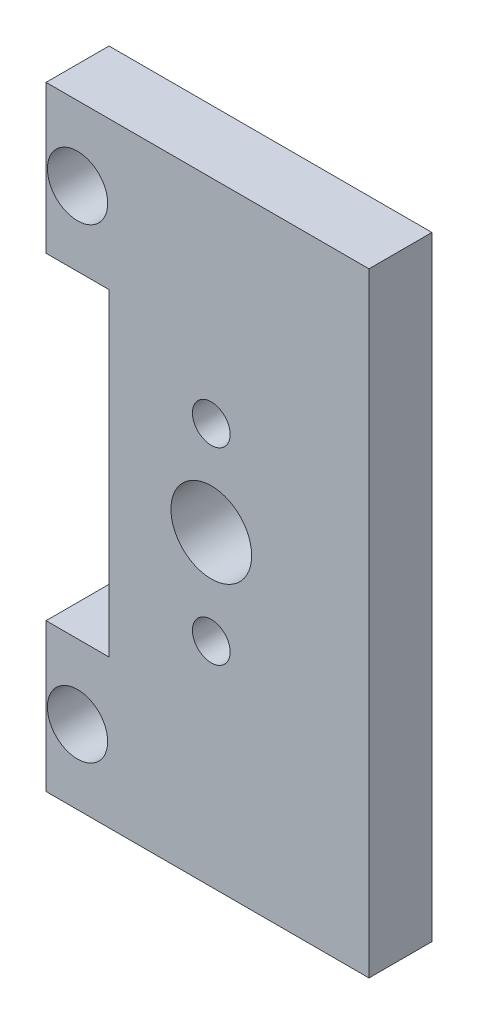
SolidWorks part; units mm, degrees
ref_plane "Front Plane" through (0, 0, 0) normal (0, 0, 1) x (1, 0, 0)
ref_plane "Top Plane" through (0, 0, 0) normal (0, 1, 0) x (1, 0, 0)
ref_plane "Right Plane" through (0, 0, 0) normal (1, 0, 0) x (0, 0, -1)
sketch "Sketch2" plane through (0, 0, 0) normal (0, 0, 1) x (1, 0, 0)
  line L0 (15.24, 14.4925) -> (0, 14.4925) construction
  line L1 (0, 0) -> (15.24, 0)
  line L2 (0, 0) -> (0, 28.985)
  line L5 (0, 28.985) -> (15.24, 28.985)
  line L6 (15.24, 0) -> (15.24, 28.985)
  line L7 (0, 6.985) -> (2.9718, 6.985)
  line L8 (0, 6.985) -> (0, 22)
  line L9 (0, 22) -> (2.9718, 22)
  line L10 (2.9718, 6.985) -> (2.9718, 22)
  circle A0 centre (1.4859, 25.4925) radius 1.4224
  circle A2 centre (1.4859, 3.4925) radius 1.4224
  circle A3 centre (7.7978, 14.4925) radius 1.905
  circle A4 centre (7.7978, 10.0475) radius 0.889
  circle A5 centre (7.7978, 18.9375) radius 0.889
  point P18 (0, 0)
  dimension "D3" = 6.985
  dimension "D7" = 1.4859
  dimension "D6" = 2.8448
  dimension "D9" = 3.81
  dimension "D11" = 1.778
  dimension "D1" = 2.9718
  dimension "D2" = 6.985
  dimension "D4" = 15.24
  dimension "D5" = 15.015
  dimension "D8" = 3.4925
  dimension "D10" = 4.826
  dimension "D12" = 4.445
extrude "Boss-Extrude1" add sketch "Sketch2" along normal blind 2.9718 contours L0 L6 L5 L2 L9 L10 A0 | L6 L0 L10 L7 L2 L1 A2 region at (0.0327, 3.4925, 0)
